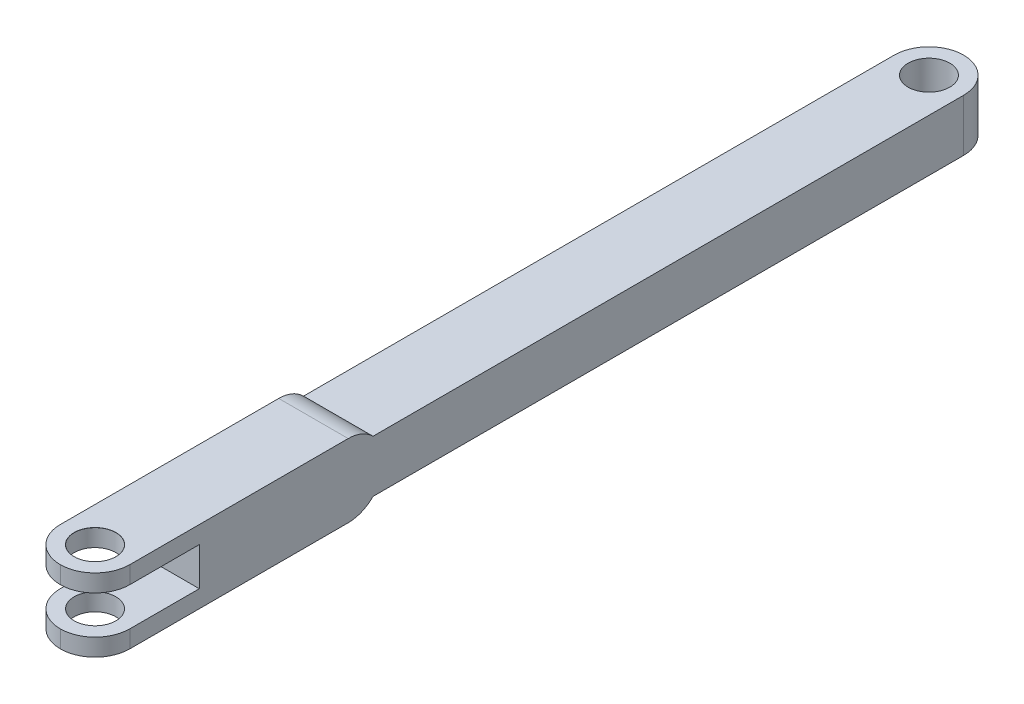
SolidWorks part; units mm, degrees
ref_plane "Plan de face" through (0, 0, 0) normal (0, 0, 1) x (1, 0, 0)
ref_plane "Plan de dessus" through (0, 0, 0) normal (0, 1, 0) x (1, 0, 0)
ref_plane "Plan de droite" through (0, 0, 0) normal (1, 0, 0) x (0, 0, -1)
sketch "Esquisse1" plane through (0, 0, 0) normal (1, 0, 0) x (0, 0, -1)
  line L0 (70, 10.5) -> (-10, 10.5)
  line L1 (-10, 10.5) -> (-10, 5.5)
  line L2 (70, 10.5) -> (70, 7.5)
  line L3 (70, 7.5) -> (250, 7.5)
  line L4 (-10, 5.5) -> (20, 5.5)
  line L5 (20, 5.5) -> (20, -5.5)
  line L6 (250, 7.5) -> (250, -7.5)
  line L7 (55, 0) -> (-55, 0) construction
  line L8 (-10, -5.5) -> (20, -5.5)
  line L9 (70, -7.5) -> (250, -7.5)
  line L10 (70, -10.5) -> (70, -7.5)
  line L11 (-10, -10.5) -> (-10, -5.5)
  line L12 (70, -10.5) -> (-10, -10.5)
  point P12 (250, 0)
  point P13 (20, 0)
  dimension "D1" = 11
  dimension "D2" = 15
  dimension "D3" = 5
  dimension "D4" = 50
  dimension "D5" = 30
  dimension "D6" = 20
  dimension "D7" = 180
extrude "Boss.-Extru.1" add sketch "Esquisse1" along normal mid plane 20
fillet "Congé1" radius 10 8 edges at (0, -10.5, -70) (0, 10.5, -70) (-10, -8, 10) (-10, 8, 10) (10, -8, 10) (10, 8, 10) (-10, 0, -250) (10, 0, -250)
sketch "Esquisse4" plane through (0, 10.5, 0) normal (0, 1, 0) x (1, 0, 0)
  line L0 (10, 240) -> (-10, 240) construction
  line L1 (0, 250) -> (0, 217.7488) construction
  point P0 (0, 0)
  point P9 (0, 240)
hole_wizard "Dégagement M102" positions "Esquisse4" profile "Esquisse5" hole size "M10" standard "ISO" end condition through all
sketch "Esquisse5" plane through (0, 10.5, 0) normal (1, 0, 0) x (0, 0, 1)
  line L0 (0, 0) -> (0, 21)
  line L1 (0, 21) -> (6, 21)
  line L2 (6, 21) -> (6, 0.025)
  line L3 (6, 0.025) -> (6.025, 0)
  line L5 (6.025, 0) -> (0, 0)
  line L6 (-6, 0.025) -> (-6.025, 0) construction
  line L11 (0, -6.35) -> (0, 107.95) construction
  dimension "Diamètre du perçage jusqu'au prochain" = 12
  dimension "Profondeur du perçage jusqu'au prochain" = 21
  dimension "Diamètre du fraisage entrant" = 12.05
  dimension "Angle du fraisage entrant" = 90
